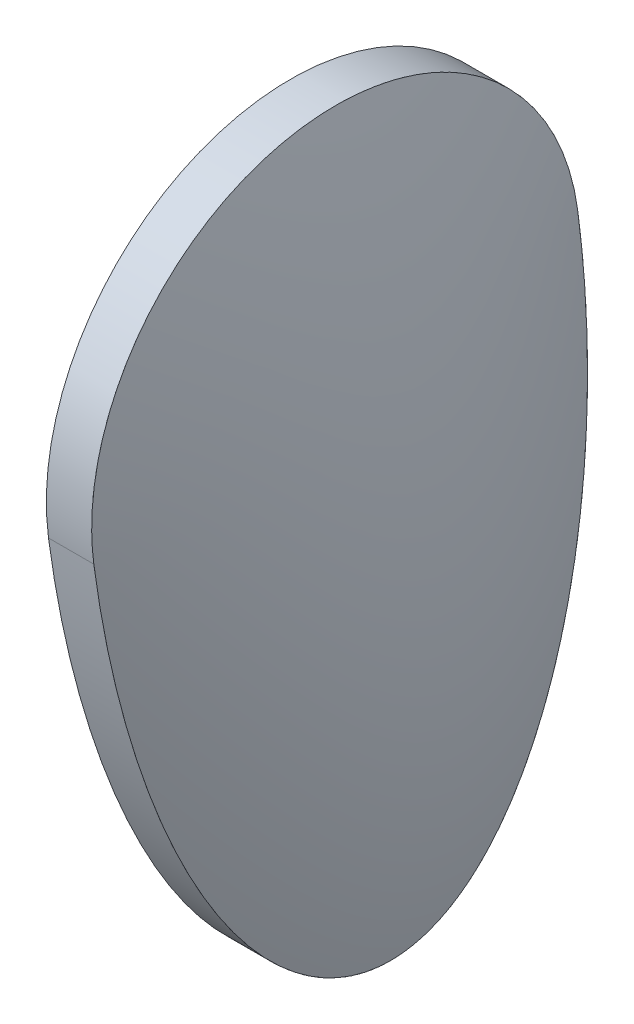
SolidWorks part; units mm, degrees
ref_plane "Plano frontal" through (0, 0, 0) normal (0, 0, 1) x (1, 0, 0)
ref_plane "Plano superior" through (0, 0, 0) normal (0, 1, 0) x (1, 0, 0)
ref_plane "Plano direito" through (0, 0, 0) normal (1, 0, 0) x (0, 0, -1)
sketch "Esboço43" plane through (0, 0, 0) normal (1, 0, 0) x (0, 0, -1)
  line L0 (0, 0) -> (0, -150) construction
  line L1 (0, -150) -> (20, -150) construction
  arc A0 (69.386, 9.2515) -> (-69.386, -9.2515) centre (0, 0) ccw
  ellipse E0 centre (0, 0) end of major axis (20, -150) minor radius 70 (-69.386, -9.2515) -> (69.386, 9.2515) ccw
  dimension "D1" = 140
  dimension "D2" = 150
  dimension "D3" = 20
extrude "Ressalto-extrusão11" add sketch "Esboço43" along normal blind 13
sketch3d "3DSketch4"
  arc A0 (13, 69.3586, 9.4543) -> (13, -149.9687, -20.2284) centre (-399.0364, -36.5209, -33.3487) cw
  arc A1 (13, 9.2515, -69.386) -> (13, -9.2515, 69.386) centre (13, 0, 0) ccw construction
  spline S0 degree 3 poles (13, -9.2515, 69.386) (13, -309.2515, 29.386) (13, -290.7485, -109.386) (13, 9.2515, -69.386) knots 0 0 0 0 1 1 1 1 weights 1 0.333333 0.333333 1 construction
  point P2 (-369.8245, 20.6877, -456.0665)
  point P8 (83, 0, 0)
surface "Superfície-Preenchimento3"
sketch "Esboço44" plane through (0, 0, 0) normal (1, 0, 0) x (0, 0, -1)
  line L0 (0, 70) -> (-25.8959, 70) construction
  circle A2 centre (-5, 28) radius 20
  spline S0 degree 3 poles (69.386, 9.2515) (69.3402, 9.5842) (69.2487, 10.2496) (69.0931, 11.2451) (68.9244, 12.2383) (68.741, 13.229) (68.5435, 14.217) (68.2109, 15.7648) (67.7009, 17.863) (66.9516, 20.4934) (65.8165, 23.9584) (64.1451, 28.2026) (62.1475, 32.3034) (59.9151, 36.2766) (56.9602, 40.8822) (53.5638, 45.1853) (49.234, 49.868) (45.2095, 53.5903) (40.8489, 56.8962) (37.0624, 59.4323) (33.1303, 61.7444) (29.0296, 63.7424) (24.8229, 65.4953) (20.5169, 67.0003) (16.1064, 68.1645) (11.6395, 69.0676) (7.1232, 69.7083) (2.5707, 69.9943) (-1.9867, 70.0133) (-7.4506, 69.7159) (-12.869, 68.8853) (-18.1923, 67.6377) (-22.565, 66.3386) (-26.8228, 64.7021) (-30.9737, 62.8208) (-35.011, 60.6977) (-38.8702, 58.266) (-42.5771, 55.6148) (-46.1256, 52.7486) (-49.4394, 49.6141) (-52.5613, 46.2939) (-56.0701, 42.0947) (-59.1579, 37.5653) (-61.8756, 32.821) (-64.3133, 27.9217) (-66.2647, 22.799) (-67.8063, 17.5533) (-68.8342, 13.109) (-69.5118, 8.5982) (-69.8414, 4.9669) (-69.9821, 2.2356) (-70.016, -0.4992) (-69.9434, -3.2333) (-69.7863, -5.6034) (-69.5935, -7.6093) (-69.4551, -8.7041) (-69.386, -9.2515) knots 0 0 0 0 0.004582 0.009165 0.013748 0.01833 0.022913 0.027495 0.039932 0.052369 0.064806 0.089675 0.114544 0.126981 0.15185 0.189142 0.201578 0.238871 0.263739 0.276177 0.301046 0.325914 0.338352 0.363221 0.38809 0.400527 0.425396 0.450265 0.462702 0.487571 0.524862 0.537299 0.562169 0.587037 0.599474 0.624344 0.649212 0.661649 0.686519 0.711387 0.723824 0.748694 0.785985 0.798423 0.823291 0.860583 0.87302 0.897889 0.922759 0.935195 0.947632 0.960069 0.972506 0.984943 0.992472 1 1 1 1 construction
  dimension "D1" = 40
  dimension "D3" = 42
  dimension "D2" = 5
  dimension "D4" = 70
extrude "Ressalto-extrusão12" add sketch "Esboço44" against normal blind 12
